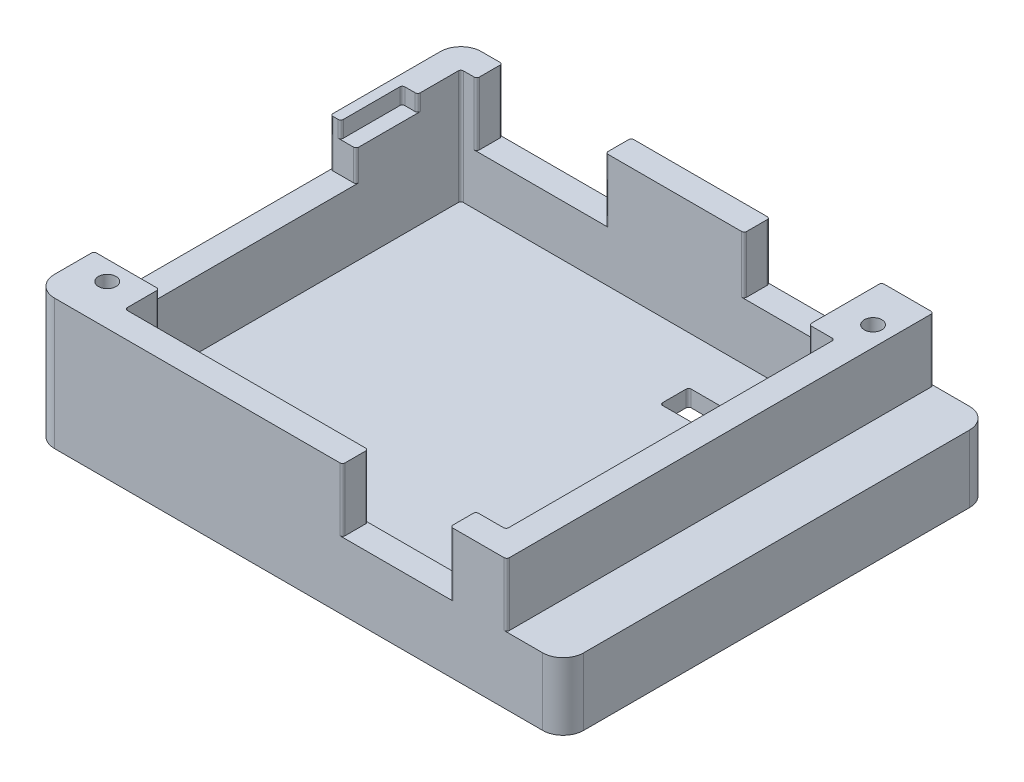
SolidWorks part; units mm, degrees
ref_plane "Front Plane" through (0, 0, 0) normal (0, 0, 1) x (1, 0, 0)
ref_plane "Top Plane" through (0, 0, 0) normal (0, 1, 0) x (1, 0, 0)
ref_plane "Right Plane" through (0, 0, 0) normal (1, 0, 0) x (0, 0, -1)
sketch "Sketch1" plane through (0, 0, 0) normal (0, 1, 0) x (1, 0, 0)
  line L1 (0, 0) -> (103.124, 0)
  line L2 (0, 0) -> (0, 83.185)
  line L3 (0, 83.185) -> (103.124, 83.185)
  line L4 (103.124, 0) -> (103.124, 83.185)
  dimension "D1" = 103.124
  dimension "D2" = 83.185
extrude "Boss-Extrude1" add sketch "Sketch1" along normal blind 25.4
sketch "Sketch2" plane through (0, 25.4, 0) normal (0, 1, 0) x (1, 0, 0)
  line L0 (0, 83.185) -> (0, 0) construction
  line L1 (5, 78.185) -> (82, 78.185)
  line L2 (5, 78.185) -> (5, 11.7)
  line L3 (12.7, 5) -> (87, 5)
  line L4 (87, 69.0118) -> (87, 5)
  line L5 (103.124, 83.185) -> (0, 83.185) construction
  line L6 (0, 0) -> (103.124, 0) construction
  line L7 (5, 11.7) -> (12.7, 11.7)
  line L8 (12.7, 11.7) -> (12.7, 5)
  line L9 (82, 78.185) -> (82, 69.0118)
  line L10 (82, 69.0118) -> (87, 69.0118)
  dimension "D1" = 5
  dimension "D2" = 5
  dimension "D3" = 82
  dimension "D4" = 5
  dimension "D5" = 11.7
  dimension "D6" = 12.7
  dimension "D7" = 77
  dimension "D8" = 14.1732
extrude "Cut-Extrude1" cut sketch "Sketch2" against normal offset from surface (22.225 mm away) 3.175 from surface up to face at (51.562, 0, -41.5925) starting at face at (51.562, 25.4, -41.5925)
sketch "Sketch3" plane through (0, 25.4, 0) normal (0, 1, 0) x (1, 0, 0)
  line L0 (0, 0) -> (103.124, 0) construction
  line L1 (103.124, 83.185) -> (92.124, 83.185)
  line L2 (103.124, 83.185) -> (103.124, 0)
  line L3 (103.124, 0) -> (92.124, 0)
  line L4 (92.124, 83.185) -> (92.124, 0)
  dimension "D1" = 11
extrude "Cut-Extrude2" cut sketch "Sketch3" against normal blind 12.3
sketch "Sketch4" plane through (0, 0, -83.185) normal (0, 0, -1) x (-1, 0, 0)
  line L0 (-92.124, 25.4) -> (0, 25.4) construction
  line L1 (-82, 25.4) -> (-60.2, 25.4)
  line L2 (-82, 25.4) -> (-82, 14.3)
  line L3 (-82, 14.3) -> (-60.2, 14.3)
  line L4 (-60.2, 25.4) -> (-60.2, 14.3)
  line L6 (0, 25.4) -> (0, 0) construction
  line L7 (-33.2, 25.4) -> (-8.1, 25.4)
  line L8 (-33.2, 25.4) -> (-33.2, 13.1)
  line L9 (-33.2, 13.1) -> (-8.1, 13.1)
  line L10 (-8.1, 25.4) -> (-8.1, 13.1)
  line L11 (-82, 3.175) -> (-82, 25.4) construction
  line L12 (-92.124, 13.1) -> (-92.124, 25.4) construction
  dimension "D1" = 10.124
  dimension "D2" = 21.8
  dimension "D3" = 11.1
  dimension "D4" = 12.3
  dimension "D5" = 27
  dimension "D6" = 8.1
  dimension "D7" = 25.1
extrude "Cut-Extrude3" cut sketch "Sketch4" against normal up to next
sketch "Sketch6" plane through (0, 0, 0) normal (-1, 0, 0) x (0, 0, 1)
  line L0 (-83.185, 25.4) -> (0, 25.4) construction
  line L1 (-11.7, 25.4) -> (-57.785, 25.4)
  line L2 (-11.7, 25.4) -> (-11.7, 16.2)
  line L3 (-11.7, 16.2) -> (-57.785, 16.2)
  line L4 (-57.785, 25.4) -> (-57.785, 16.2)
  line L5 (-83.185, 25.4) -> (-83.185, 0) construction
  line L6 (-11.7, 3.175) -> (-11.7, 25.4) construction
  dimension "D1" = 46.085
  dimension "D2" = 9.2
  dimension "D3" = 25.4
extrude "Cut-Extrude5" cut sketch "Sketch6" against normal blind 5.08
sketch "Sketch7" plane through (0, 25.4, 0) normal (0, 1, 0) x (1, 0, 0)
  line L0 (0, 83.185) -> (0, 57.785) construction
  line L1 (5, 57.785) -> (2, 57.785)
  line L2 (5, 57.785) -> (5, 69.785)
  line L3 (5, 69.785) -> (2, 69.785)
  line L4 (2, 57.785) -> (2, 69.785)
  dimension "D1" = 12
  dimension "D2" = 2
extrude "Cut-Extrude6" cut sketch "Sketch7" against normal blind 3.175
sketch "Sketch8" plane through (0, 0, 0) normal (0, -1, 0) x (1, 0, 0)
  line L1 (58.674, -63.3413) -> (69.7865, -63.3413)
  line L2 (58.674, -63.3413) -> (58.674, -68.8975)
  line L3 (58.674, -68.8975) -> (69.7865, -68.8975)
  line L4 (69.7865, -63.3413) -> (69.7865, -68.8975)
  line L6 (103.124, -83.185) -> (0, -83.185) construction
  line L8 (103.124, 0) -> (103.124, -83.185) construction
  dimension "D1" = 33.3375
  dimension "D2" = 5.5562
  dimension "D3" = 14.2875
  dimension "D4" = 11.1125
extrude "Cut-Extrude7" cut sketch "Sketch8" against normal blind 5.08
fillet "Fillet1" radius 4 4 edges at (103.124, 6.55, -83.185) (103.124, 6.55, 0) (0, 12.7, 0) (0, 12.7, -83.185)
sketch "Sketch9" plane through (0, 0, 0) normal (0, 0, 1) x (1, 0, 0)
  line L0 (4, 25.4) -> (92.124, 25.4) construction
  line L1 (81.124, 25.4) -> (60.124, 25.4)
  line L2 (81.124, 25.4) -> (81.124, 13.1)
  line L3 (81.124, 13.1) -> (60.124, 13.1)
  line L4 (60.124, 25.4) -> (60.124, 13.1)
  line L5 (92.124, 13.1) -> (92.124, 25.4) construction
  dimension "D1" = 11
  dimension "D2" = 21
  dimension "D3" = 12.3
extrude "Cut-Extrude8" cut sketch "Sketch9" against normal up to next
fillet "Fillet2" radius 0.5 31 edges at (5, 9.6875, -11.7) (0, 20.8, -11.7) (12.7, 14.2875, -11.7) (12.7, 14.2875, -5) (60.124, 19.25, -5) (60.124, 19.25, 0) (92.124, 19.25, 0) (81.124, 19.25, 0) (81.124, 19.25, -5) (87, 14.2875, -5) (87, 14.2875, -69.0118) (82, 14.2875, -69.0118) (82, 19.85, -83.185) (92.124, 19.25, -83.185) (60.2, 19.85, -83.185) (60.2, 19.85, -78.185) (33.2, 19.25, -78.185) (33.2, 19.25, -83.185) (8.1, 19.25, -83.185) (8.1, 19.25, -78.185) (5, 14.2875, -78.185) (5, 23.8125, -69.785) (2, 23.8125, -69.785) (5, 19.2125, -57.785) (2, 23.8125, -57.785) (0, 20.8, -57.785) (58.674, 1.5875, -68.8975) (82, 8.7375, -78.185) (69.7865, 1.5875, -68.8975) (69.7865, 1.5875, -63.3413) (58.674, 1.5875, -63.3413)
sketch "Sketch10" plane through (0, 25.4, 0) normal (0, 1, 0) x (1, 0, 0)
  line L0 (86.5, 69.0118) -> (82.5, 69.0118) construction
  line L1 (82, 69.5118) -> (82, 82.685) construction
  line L2 (0, 11.2) -> (0, 4) construction
  line L3 (4, 0) -> (59.624, 0) construction
  line L5 (88.265, 75.2475) -> (6.35, 75.2475) construction
  line L6 (88.265, 75.2475) -> (88.265, 7.9375) construction
  line L7 (88.265, 7.9375) -> (6.35, 7.9375) construction
  line L8 (6.35, 75.2475) -> (6.35, 7.9375) construction
  line L9 (88.265, 75.2475) -> (6.35, 7.9375) construction
  line L10 (88.265, 7.9375) -> (6.35, 75.2475) construction
  circle A0 centre (6.35, 7.9375) radius 1.7145
  point P0 (6.35, 7.9375)
  point P1 (88.265, 75.2475)
  point P15 (0, 0)
  dimension "D7" = 3.429
  dimension "D1" = 6.2357
  dimension "D2" = 6.265
  dimension "D3" = 6.35
  dimension "D4" = 7.9375
  dimension "D5" = 81.915
  dimension "D6" = 67.31
extrude "Cut-Extrude9" cut sketch "Sketch10" against normal blind 6.35
pattern_sketch "Sketch-Pattern1" of "Cut-Extrude9" driven by "Sketch10"
